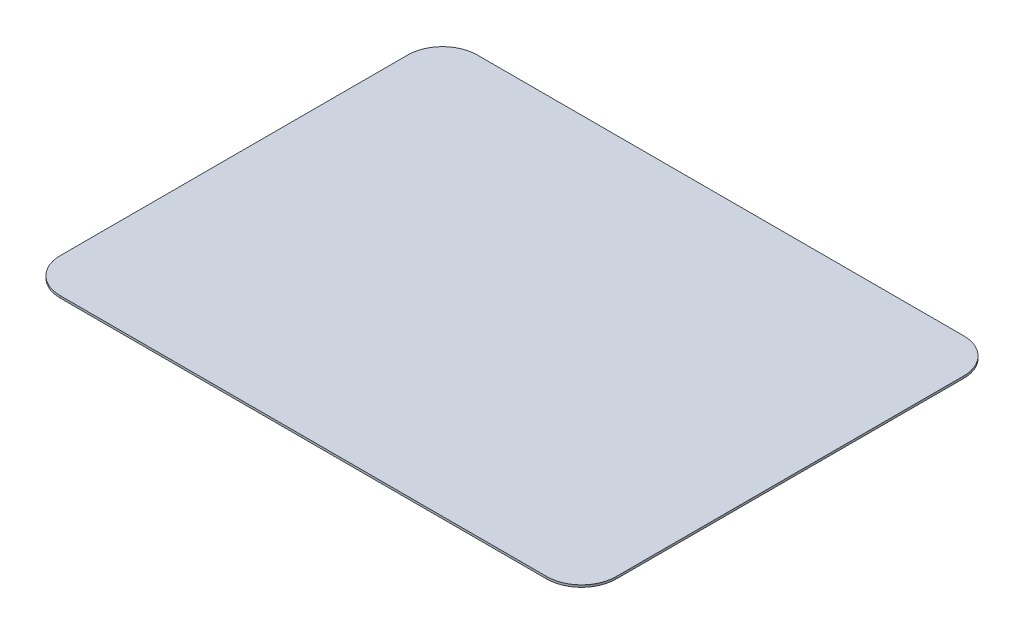
SolidWorks part; units mm, degrees
ref_plane "Front Plane" through (0, 0, 0) normal (0, 0, 1) x (1, 0, 0)
ref_plane "Top Plane" through (0, 0, 0) normal (0, 1, 0) x (1, 0, 0)
ref_plane "Right Plane" through (0, 0, 0) normal (1, 0, 0) x (0, 0, -1)
ref_plane "SheetPlane" through (0, 25.0193, 0) normal (0, 1, 0) x (1, 0, 0)
sketch "Sketch1" plane through (0, 25.0193, 0) normal (0, 1, 0) x (1, 0, 0)
  line L1 (-92.1192, -61.9656) -> (85.6808, -61.9656) construction
  line L2 (-104.8192, 77.7344) -> (-104.8192, -49.2656) construction
  line L3 (85.6808, 90.4344) -> (-92.1192, 90.4344) construction
  line L16 (98.3808, -49.2656) -> (98.3808, 77.7344)
  line L17 (-92.1192, -61.9656) -> (85.6808, -61.9656)
  line L18 (-104.8192, 77.7344) -> (-104.8192, -49.2656)
  line L19 (85.6808, 90.4344) -> (-92.1192, 90.4344)
  line L20 (98.3808, -49.2656) -> (98.3808, 77.7344) construction
  arc A0 (-92.1192, 90.4344) -> (-104.8192, 77.7344) centre (-92.1192, 77.7344) ccw construction
  arc A1 (-104.8192, -49.2656) -> (-92.1192, -61.9656) centre (-92.1192, -49.2656) ccw construction
  arc A2 (-92.1192, 90.4344) -> (-104.8192, 77.7344) centre (-92.1192, 77.7344) ccw
  arc A3 (85.6808, -61.9656) -> (98.3808, -49.2656) centre (85.6808, -49.2656) ccw construction
  arc A12 (85.6808, -61.9656) -> (98.3808, -49.2656) centre (85.6808, -49.2656) ccw
  arc A13 (98.3808, 77.7344) -> (85.6808, 90.4344) centre (85.6808, 77.7344) ccw construction
  arc A14 (98.3808, 77.7344) -> (85.6808, 90.4344) centre (85.6808, 77.7344) ccw
  arc A18 (-104.8192, -49.2656) -> (-92.1192, -61.9656) centre (-92.1192, -49.2656) ccw
extrude "MainBody" add sketch "Sketch1" along normal blind 0.7937
equation "\"SheetThickness\"= 0.03125in"
equation "\"D1@MainBody\" = \"SheetThickness\""
equation "\"SheetTolerance\"= 0.012in"
